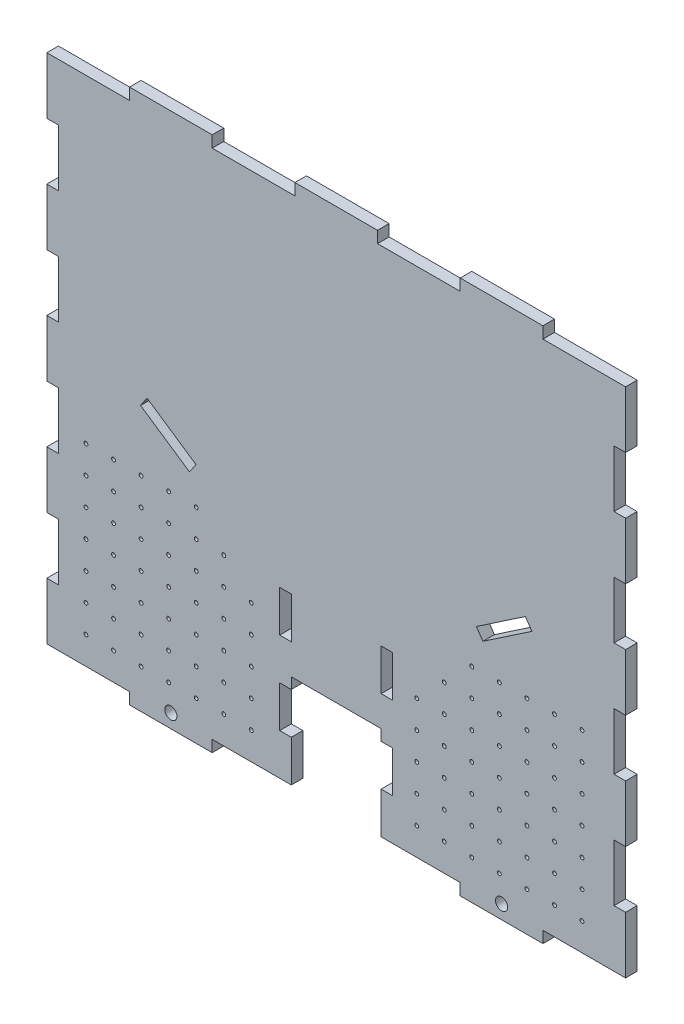
SolidWorks part; units mm, degrees
ref_plane "Front Plane" through (0, 0, 0) normal (0, 0, 1) x (1, 0, 0)
ref_plane "Top Plane" through (0, 0, 0) normal (0, 1, 0) x (1, 0, 0)
ref_plane "Right Plane" through (0, 0, 0) normal (1, 0, 0) x (0, 0, -1)
sketch "Sketch1" plane through (0, 0, 0) normal (0, 0, 1) x (1, 0, 0)
  line L1 (-240.9417, 218.2569) -> (25.7583, 218.2569)
  line L2 (-240.9417, 218.2569) -> (-240.9417, -28.3263)
  line L3 (-240.9417, -28.3263) -> (25.7583, -28.3263)
  line L4 (25.7583, 218.2569) -> (25.7583, -28.3263)
  dimension "D1" = 266.7
  dimension "D2" = 246.5832
extrude "Boss-Extrude1" add sketch "Sketch1" along normal blind 5.334
sketch "Sketch3" plane through (0, 0, 5.334) normal (0, 0, 1) x (1, 0, 0)
  line L0 (25.7583, 218.2569) -> (-240.9417, 218.2569) construction
  line L1 (-240.9417, 218.2569) -> (-202.8417, 218.2569)
  line L2 (-240.9417, 218.2569) -> (-240.9417, 212.9229)
  line L3 (-240.9417, 212.9229) -> (-202.8417, 212.9229)
  line L4 (-202.8417, 218.2569) -> (-202.8417, 212.9229)
  line L5 (-164.7417, 218.2569) -> (-126.6417, 218.2569)
  line L6 (-164.7417, 218.2569) -> (-164.7417, 212.9229)
  line L7 (-164.7417, 212.9229) -> (-126.6417, 212.9229)
  line L8 (-126.6417, 218.2569) -> (-126.6417, 212.9229)
  line L9 (25.7583, -28.3263) -> (25.7583, 218.2569) construction
  line L10 (-88.5417, 218.2569) -> (-50.4417, 218.2569)
  line L11 (-88.5417, 218.2569) -> (-88.5417, 212.9229)
  line L12 (-88.5417, 212.9229) -> (-50.4417, 212.9229)
  line L13 (-50.4417, 218.2569) -> (-50.4417, 212.9229)
  line L14 (-12.3417, 218.2569) -> (25.7583, 218.2569)
  line L15 (-12.3417, 218.2569) -> (-12.3417, 212.9229)
  line L16 (-12.3417, 212.9229) -> (25.7583, 212.9229)
  line L17 (25.7583, 218.2569) -> (25.7583, 212.9229)
  line L18 (-202.8417, 212.9229) -> (-164.7417, 212.9229) construction
  line L19 (-12.3417, 212.9229) -> (-50.4417, 212.9229) construction
  line L20 (-88.5417, 212.9229) -> (-126.6417, 212.9229) construction
  line L21 (-240.9417, 94.9653) -> (25.7583, 94.9653) construction
  line L22 (-240.9417, 218.2569) -> (-240.9417, -28.3263) construction
  line L23 (-88.5417, -22.9923) -> (-126.6417, -22.9923) construction
  line L24 (-12.3417, -22.9923) -> (-50.4417, -22.9923) construction
  line L25 (-202.8417, -22.9923) -> (-164.7417, -22.9923) construction
  line L26 (25.7583, -28.3263) -> (25.7583, -22.9923)
  line L27 (-12.3417, -22.9923) -> (25.7583, -22.9923)
  line L28 (-12.3417, -28.3263) -> (-12.3417, -22.9923)
  line L29 (-12.3417, -28.3263) -> (25.7583, -28.3263)
  line L30 (-50.4417, -28.3263) -> (-50.4417, -22.9923)
  line L31 (-88.5417, -22.9923) -> (-50.4417, -22.9923)
  line L32 (-88.5417, -28.3263) -> (-88.5417, -22.9923)
  line L33 (-88.5417, -28.3263) -> (-50.4417, -28.3263)
  line L34 (-126.6417, -28.3263) -> (-126.6417, -22.9923)
  line L35 (-164.7417, -22.9923) -> (-126.6417, -22.9923)
  line L36 (-164.7417, -28.3263) -> (-164.7417, -22.9923)
  line L37 (-164.7417, -28.3263) -> (-126.6417, -28.3263)
  line L38 (-202.8417, -28.3263) -> (-202.8417, -22.9923)
  line L39 (-240.9417, -22.9923) -> (-202.8417, -22.9923)
  line L40 (-240.9417, -28.3263) -> (-240.9417, -22.9923)
  line L41 (-240.9417, -28.3263) -> (-202.8417, -28.3263)
  dimension "D1" = 5.334
extrude "Cut-Extrude1" cut sketch "Sketch3" against normal through all
sketch "Sketch4" plane through (0, 0, 5.334) normal (0, 0, 1) x (1, 0, 0)
  line L0 (-128.2927, -22.9923) -> (-128.2927, 53.2077) construction
  line L1 (-126.6417, -22.9923) -> (-164.7417, -22.9923) construction
  line L2 (-128.2927, 53.2077) -> (-240.9417, 129.4077) construction
  line L3 (-133.6267, 34.1577) -> (-133.6267, 15.1077) construction
  line L4 (-240.9417, 212.9229) -> (-240.9417, -22.9923) construction
  line L5 (-240.9417, 212.9229) -> (-202.8417, 212.9229) construction
  line L6 (-133.6267, -3.9423) -> (-133.6267, -22.9923) construction
  line L7 (-128.2927, 53.2077) -> (-133.6267, 53.2077)
  line L8 (-128.2927, 53.2077) -> (-128.2927, 34.1577)
  line L9 (-128.2927, 34.1577) -> (-133.6267, 34.1577)
  line L10 (-133.6267, 53.2077) -> (-133.6267, 34.1577)
  line L11 (-128.2927, 15.1077) -> (-133.6267, 15.1077)
  line L12 (-128.2927, 15.1077) -> (-128.2927, -3.9423)
  line L13 (-128.2927, -3.9423) -> (-133.6267, -3.9423)
  line L14 (-133.6267, 15.1077) -> (-133.6267, -3.9423)
  line L15 (-172.2005, 82.9085) -> (-175.1891, 78.4904)
  line L16 (-172.2005, 82.9085) -> (-194.7652, 98.1722)
  line L17 (-175.1891, 78.4904) -> (-197.7538, 93.754)
  line L18 (-194.7652, 98.1722) -> (-197.7538, 93.754)
  line L19 (-107.5917, 218.2569) -> (-107.5917, -28.3263) construction
  line L20 (-88.5417, 218.2569) -> (-126.6417, 218.2569) construction
  line L21 (-126.6417, -28.3263) -> (-88.5417, -28.3263) construction
  line L22 (-81.5567, -3.9423) -> (-81.5567, -22.9923) construction
  line L23 (-81.5567, 34.1577) -> (-81.5567, 15.1077) construction
  line L24 (-86.8907, 53.2077) -> (25.7583, 129.4077) construction
  line L25 (-86.8907, -22.9923) -> (-86.8907, 53.2077) construction
  line L26 (-20.4182, 98.1722) -> (-17.4297, 93.754)
  line L27 (-39.9944, 78.4904) -> (-17.4297, 93.754)
  line L28 (-42.983, 82.9085) -> (-20.4182, 98.1722)
  line L29 (-42.983, 82.9085) -> (-39.9944, 78.4904)
  line L30 (-81.5567, 15.1077) -> (-81.5567, -3.9423)
  line L31 (-86.8907, -3.9423) -> (-81.5567, -3.9423)
  line L32 (-86.8907, 15.1077) -> (-86.8907, -3.9423)
  line L33 (-86.8907, 15.1077) -> (-81.5567, 15.1077)
  line L34 (-81.5567, 53.2077) -> (-81.5567, 34.1577)
  line L35 (-86.8907, 34.1577) -> (-81.5567, 34.1577)
  line L36 (-86.8907, 53.2077) -> (-86.8907, 34.1577)
  line L37 (-86.8907, 53.2077) -> (-81.5567, 53.2077)
  dimension "D1" = 76.2
  dimension "D2" = 76.2
  dimension "D3" = 83.5152
  dimension "D4" = 112.649
  dimension "D5" = 5.334
  dimension "D6" = 5.334
extrude "Cut-Extrude2" cut sketch "Sketch4" against normal through all
sketch "Sketch5" plane through (0, 0, 5.334) normal (0, 0, 1) x (1, 0, 0)
  line L0 (-240.9417, 212.9229) -> (-240.9417, -22.9923) construction
  line L1 (-240.9417, 186.7101) -> (-235.6077, 186.7101)
  line L2 (-240.9417, 186.7101) -> (-240.9417, 160.4973)
  line L3 (-240.9417, 160.4973) -> (-235.6077, 160.4973)
  line L4 (-235.6077, 186.7101) -> (-235.6077, 160.4973)
  line L5 (-235.6077, 186.7101) -> (-235.6077, 212.9229) construction
  line L6 (-240.9417, 134.2845) -> (-235.6077, 134.2845)
  line L7 (-240.9417, 134.2845) -> (-240.9417, 108.0717)
  line L8 (-240.9417, 108.0717) -> (-235.6077, 108.0717)
  line L9 (-235.6077, 134.2845) -> (-235.6077, 108.0717)
  line L10 (-240.9417, 81.8589) -> (-235.6077, 81.8589)
  line L11 (-240.9417, 81.8589) -> (-240.9417, 55.6461)
  line L12 (-240.9417, 55.6461) -> (-235.6077, 55.6461)
  line L13 (-235.6077, 81.8589) -> (-235.6077, 55.6461)
  line L14 (-240.9417, 29.4333) -> (-235.6077, 29.4333)
  line L15 (-240.9417, 29.4333) -> (-240.9417, 3.2205)
  line L16 (-240.9417, 3.2205) -> (-235.6077, 3.2205)
  line L17 (-235.6077, 29.4333) -> (-235.6077, 3.2205)
  line L18 (-240.9417, 212.9229) -> (-202.8417, 212.9229) construction
  line L19 (-235.6077, 160.4973) -> (-235.6077, 134.2845) construction
  line L20 (-235.6077, 108.0717) -> (-235.6077, 81.8589) construction
  line L21 (-235.6077, 55.6461) -> (-235.6077, 29.4333) construction
  line L22 (-235.6077, 3.2205) -> (-235.6077, -22.9923) construction
  line L23 (-202.8417, -22.9923) -> (-240.9417, -22.9923) construction
  line L24 (-107.5917, 218.2569) -> (-107.5917, -28.3263) construction
  line L25 (-88.5417, 218.2569) -> (-126.6417, 218.2569) construction
  line L26 (-126.6417, -28.3263) -> (-88.5417, -28.3263) construction
  line L27 (20.4243, 3.2205) -> (20.4243, -22.9923) construction
  line L28 (20.4243, 55.6461) -> (20.4243, 29.4333) construction
  line L29 (20.4243, 108.0717) -> (20.4243, 81.8589) construction
  line L30 (20.4243, 160.4973) -> (20.4243, 134.2845) construction
  line L31 (20.4243, 186.7101) -> (20.4243, 212.9229) construction
  line L32 (20.4243, 29.4333) -> (20.4243, 3.2205)
  line L33 (25.7583, 3.2205) -> (20.4243, 3.2205)
  line L34 (25.7583, 29.4333) -> (25.7583, 3.2205)
  line L35 (25.7583, 29.4333) -> (20.4243, 29.4333)
  line L36 (20.4243, 81.8589) -> (20.4243, 55.6461)
  line L37 (25.7583, 55.6461) -> (20.4243, 55.6461)
  line L38 (25.7583, 81.8589) -> (25.7583, 55.6461)
  line L39 (25.7583, 81.8589) -> (20.4243, 81.8589)
  line L40 (20.4243, 134.2845) -> (20.4243, 108.0717)
  line L41 (25.7583, 108.0717) -> (20.4243, 108.0717)
  line L42 (25.7583, 134.2845) -> (25.7583, 108.0717)
  line L43 (25.7583, 134.2845) -> (20.4243, 134.2845)
  line L44 (20.4243, 186.7101) -> (20.4243, 160.4973)
  line L45 (25.7583, 160.4973) -> (20.4243, 160.4973)
  line L46 (25.7583, 186.7101) -> (25.7583, 160.4973)
  line L47 (25.7583, 186.7101) -> (20.4243, 186.7101)
  dimension "D1" = 5.334
extrude "Cut-Extrude3" cut sketch "Sketch5" against normal through all
sketch "Sketch6" plane through (0, 0, 5.334) normal (0, 0, 1) x (1, 0, 0)
  line L0 (-202.8417, -22.9923) -> (-240.9417, -22.9923) construction
  line L2 (-235.6077, 3.2205) -> (-235.6077, 29.4333) construction
  line L3 (-222.9077, -10.2923) -> (-210.2077, -10.2923) construction
  circle A0 centre (-222.9077, -10.2923) radius 0.889
  circle A1 centre (-210.2077, -10.2923) radius 0.889
  circle A2 centre (-197.5077, -10.2923) radius 0.889
  circle A3 centre (-184.8077, -10.2923) radius 0.889
  circle A4 centre (-172.1077, -10.2923) radius 0.889
  circle A5 centre (-159.4077, -10.2923) radius 0.889
  circle A6 centre (-146.7077, -10.2923) radius 0.889
  circle A7 centre (-134.0077, -10.2923) radius 0.889 [skipped]
  circle A8 centre (-121.3077, -10.2923) radius 0.889 [skipped]
  circle A9 centre (-108.6077, -10.2923) radius 0.889 [skipped]
  circle A10 centre (-95.9077, -10.2923) radius 0.889 [skipped]
  circle A11 centre (-83.2077, -10.2923) radius 0.889 [skipped]
  circle A12 centre (-70.5077, -10.2923) radius 0.889
  circle A13 centre (-57.8077, -10.2923) radius 0.889
  circle A14 centre (-45.1077, -10.2923) radius 0.889
  circle A15 centre (-32.4077, -10.2923) radius 0.889
  circle A16 centre (-19.7077, -10.2923) radius 0.889
  circle A17 centre (-7.0077, -10.2923) radius 0.889
  circle A18 centre (5.6923, -10.2923) radius 0.889
  circle A19 centre (-210.2077, 2.4077) radius 0.889
  circle A20 centre (-197.5077, 2.4077) radius 0.889
  circle A21 centre (-184.8077, 2.4077) radius 0.889
  circle A22 centre (-172.1077, 2.4077) radius 0.889
  circle A23 centre (-159.4077, 2.4077) radius 0.889
  circle A24 centre (-146.7077, 2.4077) radius 0.889
  circle A25 centre (-134.0077, 2.4077) radius 0.889 [skipped]
  circle A26 centre (-121.3077, 2.4077) radius 0.889 [skipped]
  circle A27 centre (-108.6077, 2.4077) radius 0.889 [skipped]
  circle A28 centre (-95.9077, 2.4077) radius 0.889 [skipped]
  circle A29 centre (-83.2077, 2.4077) radius 0.889 [skipped]
  circle A30 centre (-70.5077, 2.4077) radius 0.889
  circle A31 centre (-57.8077, 2.4077) radius 0.889
  circle A32 centre (-45.1077, 2.4077) radius 0.889
  circle A33 centre (-32.4077, 2.4077) radius 0.889
  circle A34 centre (-19.7077, 2.4077) radius 0.889
  circle A35 centre (-7.0077, 2.4077) radius 0.889
  circle A36 centre (5.6923, 2.4077) radius 0.889
  circle A37 centre (-210.2077, 15.1077) radius 0.889
  circle A38 centre (-197.5077, 15.1077) radius 0.889
  circle A39 centre (-184.8077, 15.1077) radius 0.889
  circle A40 centre (-172.1077, 15.1077) radius 0.889
  circle A41 centre (-159.4077, 15.1077) radius 0.889
  circle A42 centre (-146.7077, 15.1077) radius 0.889
  circle A43 centre (-134.0077, 15.1077) radius 0.889 [skipped]
  circle A44 centre (-121.3077, 15.1077) radius 0.889 [skipped]
  circle A45 centre (-108.6077, 15.1077) radius 0.889 [skipped]
  circle A46 centre (-95.9077, 15.1077) radius 0.889 [skipped]
  circle A47 centre (-83.2077, 15.1077) radius 0.889 [skipped]
  circle A48 centre (-70.5077, 15.1077) radius 0.889
  circle A49 centre (-57.8077, 15.1077) radius 0.889
  circle A50 centre (-45.1077, 15.1077) radius 0.889
  circle A51 centre (-32.4077, 15.1077) radius 0.889
  circle A52 centre (-19.7077, 15.1077) radius 0.889
  circle A53 centre (-7.0077, 15.1077) radius 0.889
  circle A54 centre (5.6923, 15.1077) radius 0.889
  circle A55 centre (-210.2077, 27.8077) radius 0.889
  circle A56 centre (-197.5077, 27.8077) radius 0.889
  circle A57 centre (-184.8077, 27.8077) radius 0.889
  circle A58 centre (-172.1077, 27.8077) radius 0.889
  circle A59 centre (-159.4077, 27.8077) radius 0.889
  circle A60 centre (-146.7077, 27.8077) radius 0.889
  circle A61 centre (-134.0077, 27.8077) radius 0.889 [skipped]
  circle A62 centre (-121.3077, 27.8077) radius 0.889 [skipped]
  circle A63 centre (-108.6077, 27.8077) radius 0.889 [skipped]
  circle A64 centre (-95.9077, 27.8077) radius 0.889 [skipped]
  circle A65 centre (-83.2077, 27.8077) radius 0.889 [skipped]
  circle A66 centre (-70.5077, 27.8077) radius 0.889
  circle A67 centre (-57.8077, 27.8077) radius 0.889
  circle A68 centre (-45.1077, 27.8077) radius 0.889
  circle A69 centre (-32.4077, 27.8077) radius 0.889
  circle A70 centre (-19.7077, 27.8077) radius 0.889
  circle A71 centre (-7.0077, 27.8077) radius 0.889
  circle A72 centre (5.6923, 27.8077) radius 0.889
  circle A73 centre (-210.2077, 40.5077) radius 0.889
  circle A74 centre (-197.5077, 40.5077) radius 0.889
  circle A75 centre (-184.8077, 40.5077) radius 0.889
  circle A76 centre (-172.1077, 40.5077) radius 0.889
  circle A77 centre (-159.4077, 40.5077) radius 0.889
  circle A78 centre (-146.7077, 40.5077) radius 0.889
  circle A79 centre (-134.0077, 40.5077) radius 0.889 [skipped]
  circle A80 centre (-121.3077, 40.5077) radius 0.889 [skipped]
  circle A81 centre (-108.6077, 40.5077) radius 0.889 [skipped]
  circle A82 centre (-95.9077, 40.5077) radius 0.889 [skipped]
  circle A83 centre (-83.2077, 40.5077) radius 0.889 [skipped]
  circle A84 centre (-70.5077, 40.5077) radius 0.889
  circle A85 centre (-57.8077, 40.5077) radius 0.889
  circle A86 centre (-45.1077, 40.5077) radius 0.889
  circle A87 centre (-32.4077, 40.5077) radius 0.889
  circle A88 centre (-19.7077, 40.5077) radius 0.889
  circle A89 centre (-7.0077, 40.5077) radius 0.889
  circle A90 centre (5.6923, 40.5077) radius 0.889
  circle A91 centre (-210.2077, 53.2077) radius 0.889
  circle A92 centre (-197.5077, 53.2077) radius 0.889
  circle A93 centre (-184.8077, 53.2077) radius 0.889
  circle A94 centre (-172.1077, 53.2077) radius 0.889
  circle A95 centre (-159.4077, 53.2077) radius 0.889
  circle A96 centre (-146.7077, 53.2077) radius 0.889 [skipped]
  circle A97 centre (-134.0077, 53.2077) radius 0.889 [skipped]
  circle A98 centre (-121.3077, 53.2077) radius 0.889 [skipped]
  circle A99 centre (-108.6077, 53.2077) radius 0.889 [skipped]
  circle A100 centre (-95.9077, 53.2077) radius 0.889 [skipped]
  circle A101 centre (-83.2077, 53.2077) radius 0.889 [skipped]
  circle A102 centre (-70.5077, 53.2077) radius 0.889 [skipped]
  circle A103 centre (-57.8077, 53.2077) radius 0.889
  circle A104 centre (-45.1077, 53.2077) radius 0.889
  circle A105 centre (-32.4077, 53.2077) radius 0.889
  circle A106 centre (-19.7077, 53.2077) radius 0.889
  circle A107 centre (-7.0077, 53.2077) radius 0.889
  circle A108 centre (5.6923, 53.2077) radius 0.889
  circle A109 centre (-210.2077, 65.9077) radius 0.889
  circle A110 centre (-197.5077, 65.9077) radius 0.889
  circle A111 centre (-184.8077, 65.9077) radius 0.889
  circle A112 centre (-172.1077, 65.9077) radius 0.889
  circle A113 centre (-159.4077, 65.9077) radius 0.889 [skipped]
  circle A114 centre (-146.7077, 65.9077) radius 0.889 [skipped]
  circle A115 centre (-134.0077, 65.9077) radius 0.889 [skipped]
  circle A116 centre (-121.3077, 65.9077) radius 0.889 [skipped]
  circle A117 centre (-108.6077, 65.9077) radius 0.889 [skipped]
  circle A118 centre (-95.9077, 65.9077) radius 0.889 [skipped]
  circle A119 centre (-83.2077, 65.9077) radius 0.889 [skipped]
  circle A120 centre (-70.5077, 65.9077) radius 0.889 [skipped]
  circle A121 centre (-57.8077, 65.9077) radius 0.889 [skipped]
  circle A122 centre (-45.1077, 65.9077) radius 0.889
  circle A123 centre (-32.4077, 65.9077) radius 0.889
  circle A124 centre (-19.7077, 65.9077) radius 0.889
  circle A125 centre (-7.0077, 65.9077) radius 0.889
  circle A126 centre (5.6923, 65.9077) radius 0.889
  circle A127 centre (-222.9077, 2.4077) radius 0.889
  circle A128 centre (-222.9077, 15.1077) radius 0.889
  circle A129 centre (-222.9077, 27.8077) radius 0.889
  circle A130 centre (-222.9077, 40.5077) radius 0.889
  circle A131 centre (-222.9077, 53.2077) radius 0.889
  circle A132 centre (-222.9077, 65.9077) radius 0.889
  dimension "D1" = 12.7
  dimension "D2" = 12.7
  dimension "D6" = 1.778
  dimension "D5" = 12.7
  dimension "D3" = 19
  dimension "D4" = 7
extrude "Cut-Extrude4" cut sketch "Sketch6" against normal through all
sketch "Sketch7" plane through (0, 0, 5.334) normal (0, 0, 1) x (1, 0, 0)
  line L0 (-88.5417, -28.3263) -> (-50.4417, -28.3263) construction
  line L2 (-164.7417, -28.3263) -> (-126.6417, -28.3263) construction
  line L3 (-128.2927, 0) -> (-128.2927, -28.3263) construction
  line L4 (-128.2927, -3.9423) -> (-128.2927, 15.1077) construction
  line L5 (-86.8907, 0) -> (-86.8907, -28.3263) construction
  line L6 (-86.8907, 15.1077) -> (-86.8907, -3.9423) construction
  line L8 (-128.2927, -28.3263) -> (-86.8907, -28.3263)
  line L9 (-128.2927, -28.3263) -> (-128.2927, 20.1877)
  line L10 (-128.2927, 20.1877) -> (-86.8907, 20.1877)
  line L11 (-86.8907, -28.3263) -> (-86.8907, 20.1877)
  dimension "D1" = 48.514
extrude "Cut-Extrude5" cut sketch "Sketch7" against normal through all
sketch "Sketch8" plane through (0, 0, 5.334) normal (0, 0, 1) x (1, 0, 0)
  line L0 (-202.8417, -28.3263) -> (-164.7417, -28.3263) construction
  line L1 (-164.7417, -27.1144) -> (-202.8417, -27.1144) construction
  line L2 (-164.7417, -22.9923) -> (-164.7417, -28.3263) construction
  line L3 (-202.8417, -28.3263) -> (-202.8417, -22.9923) construction
  line L4 (-183.7917, -27.1144) -> (-183.7917, -12.5958) construction
  line L5 (-107.5917, 20.1877) -> (-107.5917, 125.8068) construction
  line L6 (-86.8907, 20.1877) -> (-128.2927, 20.1877) construction
  circle A0 centre (-183.7917, -21.9763) radius 2.794
  circle A1 centre (-31.3917, -21.9763) radius 2.794
  dimension "D1" = 5.588
  dimension "D2" = 6.35
  dimension "D3" = 0
extrude "Cut-Extrude6" cut sketch "Sketch8" against normal through all
equation "\"MDF\"= .21in"
equation "\"Foamcore\"= .13in"
equation "\"Gmaterial\"= \"MDF\""
equation "\"D1@Boss-Extrude1\"=\"MDF\""
equation "\"D1@Sketch3\"=\"MDF\""
equation "\"D5@Sketch4\"=\"MDF\""
equation "\"D6@Sketch4\"=\"MDF\""
equation "\"D1@Sketch5\"=\"MDF\""
equation "\"D1@Sketch7\"=\"MDF\"+1.7"
